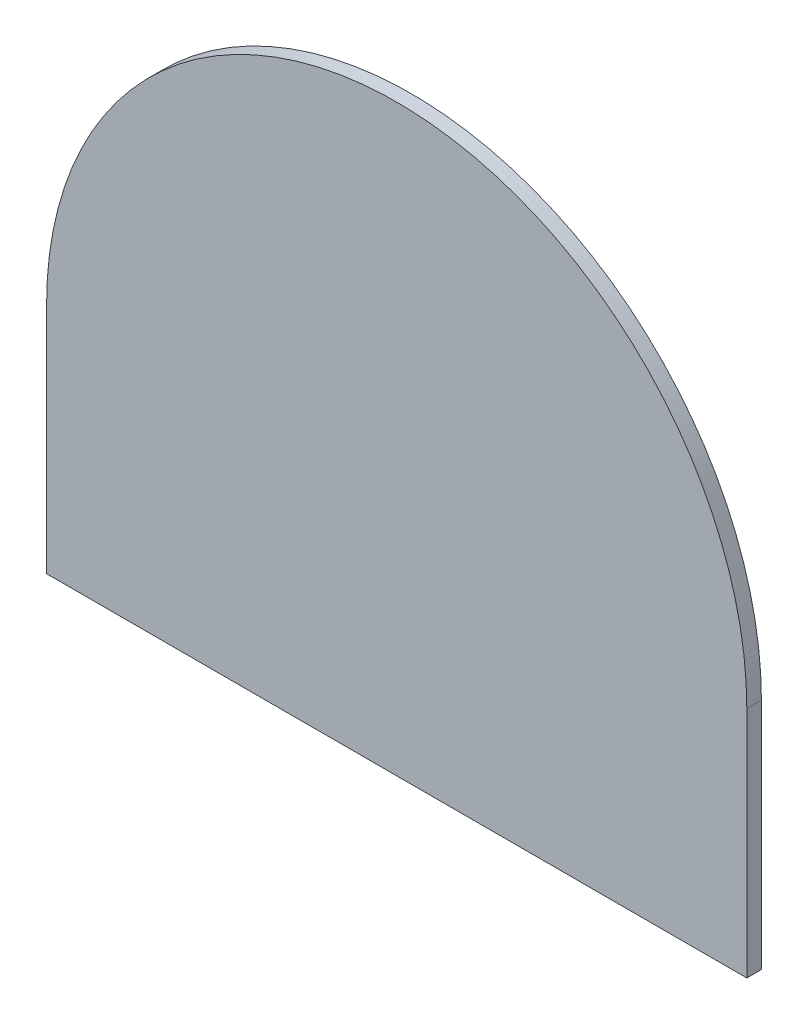
SolidWorks part; units mm, degrees
ref_plane "Front Plane" through (0, 0, 0) normal (0, 0, 1) x (1, 0, 0)
ref_plane "Top Plane" through (0, 0, 0) normal (0, 1, 0) x (1, 0, 0)
ref_plane "Right Plane" through (0, 0, 0) normal (1, 0, 0) x (0, 0, -1)
sketch "Sketch1" plane through (0, 0, 0) normal (0, 0, 1) x (1, 0, 0)
  line L0 (-228.6, -36.83) -> (-228.6, -189.23)
  line L1 (-228.6, -189.23) -> (228.6, -189.23)
  line L2 (-228.6, -189.23) -> (-228.6, 191.77) construction
  line L3 (-228.6, 191.77) -> (228.6, 191.77) construction
  line L4 (228.6, -189.23) -> (228.6, 191.77) construction
  line L5 (228.6, -36.83) -> (228.6, -189.23)
  circle A0 centre (0, 0) radius 127 construction
  arc A2 (228.6, -36.83) -> (-228.6, -36.83) centre (0, -36.83) ccw
  dimension "D1" = 254
  dimension "D4" = 189.23
  dimension "D5" = 228.6
  dimension "D2" = 457.2
  dimension "D3" = 381
extrude "Boss-Extrude1" add sketch "Sketch1" along normal blind 9.525
